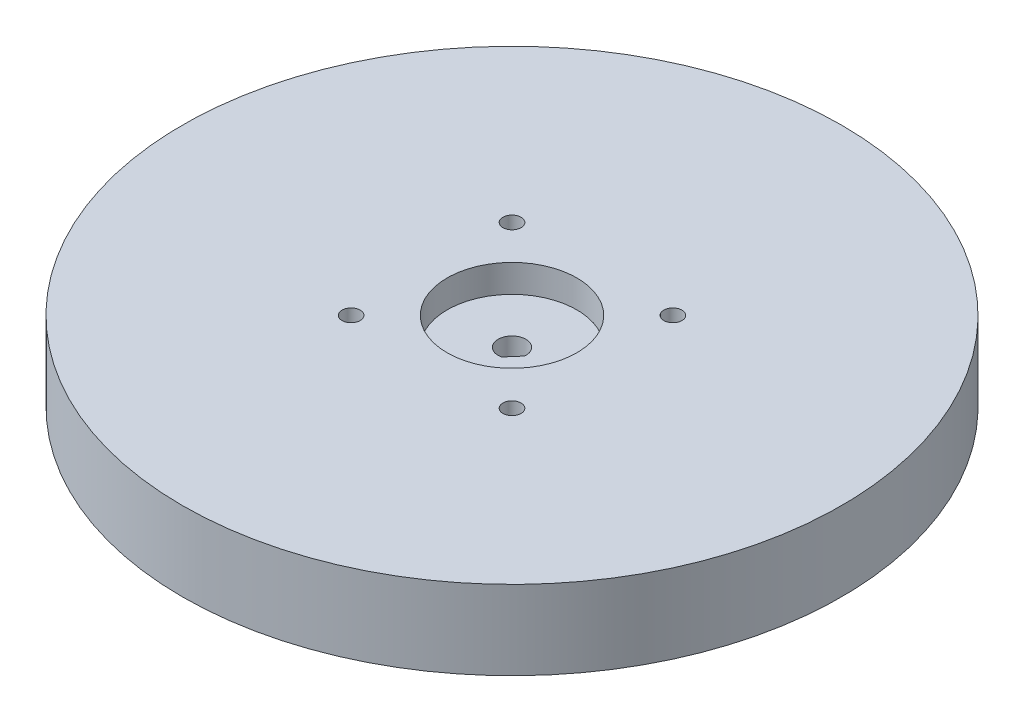
SolidWorks part; units mm, degrees
ref_plane "Front Plane" through (0, 0, 0) normal (0, 0, 1) x (1, 0, 0)
ref_plane "Top Plane" through (0, 0, 0) normal (0, 1, 0) x (1, 0, 0)
ref_plane "Right Plane" through (0, 0, 0) normal (1, 0, 0) x (0, 0, -1)
sketch "Sketch2" plane through (0, 0, 0) normal (0, 1, 0) x (1, 0, 0)
  circle A1 centre (0, 0) radius 63.5
  dimension "D1" = 127
extrude "Boss-Extrude1" add sketch "Sketch2" along normal blind 15.24 contours A1 | A1 | A1 | A1 | A1 | A1 | A1 | A1 | A1 | A1 | A1 | A1 | A1 | A1 | A1 | A1 | A1 | A1 | A1 | A1 | A1 | A1 | A1 | A1 | A1 | A1 | A1 | A1 | A1 | A1 | A1 | A1 | A1 | A1 | A1 | A1 | A1 | A1 | A1 | A1 | A1 | A1 | A1 | A1 | A1 | A1 region at (0, 0, 0)
sketch "Sketch3" plane through (0, 15.24, 0) normal (0, 1, 0) x (1, 0, 0)
  line L0 (0.6187, -2.6108) -> (2.6708, -0.2566)
  circle A5 centre (0, 0) radius 2.6831
  dimension "D1" = 5.3662
extrude "Cut-Extrude3" cut sketch "Sketch3" against normal through all contours L0 A5 region at (-0.0888, 15.24, -0.0774)
sketch "Sketch4" plane through (0, 15.24, 0) normal (0, 1, 0) x (1, 0, 0)
  line L0 (-15.5, -15.5) -> (15.5, 15.5) construction
  circle A0 centre (-15.5, 15.5) radius 1.75
  circle A1 centre (15.5, 15.5) radius 1.75
  circle A2 centre (15.5, -15.5) radius 1.75
  circle A3 centre (-15.5, -15.5) radius 1.75
  point P8 (0, 0)
  dimension "D1" = 3.5
  dimension "D5" = 31
  dimension "D6" = 31
extrude "Cut-Extrude4" cut sketch "Sketch4" against normal blind 55.626
sketch "Sketch5" plane through (0, 15.24, 0) normal (0, 1, 0) x (1, 0, 0)
  circle A0 centre (0, 0) radius 12.5
  dimension "D1" = 25
extrude "Cut-Extrude5" cut sketch "Sketch5" against normal blind 5.334
